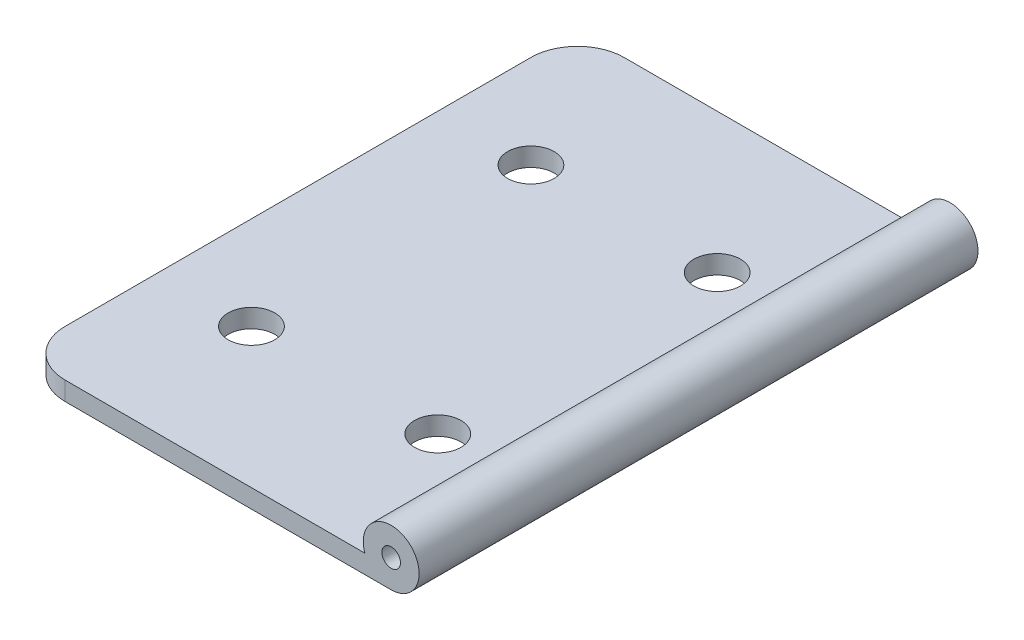
SolidWorks part; units mm, degrees
ref_plane "Front Plane" through (0, 0, 0) normal (0, 0, 1) x (1, 0, 0)
ref_plane "Top Plane" through (0, 0, 0) normal (0, 1, 0) x (1, 0, 0)
ref_plane "Right Plane" through (0, 0, 0) normal (1, 0, 0) x (0, 0, -1)
sketch "Sketch1" plane through (0, 0, 0) normal (0, 1, 0) x (1, 0, 0)
  line L0 (-32.5714, 0) -> (50.2857, 0) construction
  line L1 (0, 66.5714) -> (0, -65.7143) construction
  line L2 (-40, 30) -> (0, 30)
  line L3 (-40, 30) -> (-40, -30)
  line L4 (-40, -30) -> (0, -30)
  line L5 (0, 30) -> (0, -30)
  line L6 (-40, 30) -> (0, -30) construction
  line L7 (-40, -30) -> (0, 30) construction
  line L8 (-20, 30) -> (-20, -30) construction
  circle A0 centre (-30, 15) radius 2.5
  circle A1 centre (-10, 15) radius 2.5
  circle A2 centre (-10, -15) radius 2.5
  circle A3 centre (-30, -15) radius 2.5
  point P1 (-20, 0)
  dimension "D4" = 5
  dimension "D1" = 40
  dimension "D2" = 60
  dimension "D3" = 20
extrude "Boss-Extrude1" add sketch "Sketch1" along normal blind 2
fillet "Fillet1" radius 5 2 edges at (-40, 1, -30) (-40, 1, 30)
sketch "Sketch2" plane through (0, 0, 30) normal (0, 0, 1) x (1, 0, 0)
  line L0 (0, 3) -> (0, 2) construction
  line L1 (0, 2) -> (0, 0) construction
  circle A0 centre (0, 3) radius 3
  circle A1 centre (0, 3) radius 1
  dimension "D1" = 2
extrude "Boss-Extrude2" add sketch "Sketch2" against normal up to surface (60 mm away) up to face at (-17.5, 1, -30)
sketch "Sketch3" [suppressed] plane through (0, 0, 0) normal (0, -1, 0) x (1, 0, 0)
  line L0 (3, 0) -> (-40, 0) construction
  line L1 (3, -30) -> (3, 30) construction
  line L2 (-40, -25) -> (-40, 25) construction
  line L3 (3, 20) -> (-40, 20)
  line L4 (-35, 30) -> (0, 30) construction
  line L5 (3, -20) -> (-40, -20)
  line L7 (-3, -30) -> (3, -30)
  line L8 (-3, -30) -> (-3, 30)
  line L9 (-3, 30) -> (3, 30)
  line L10 (3, -30) -> (3, 30)
  line L11 (-3, -30) -> (3, 30) construction
  line L12 (-3, 30) -> (3, -30) construction
  point P12 (0, 0)
  dimension "D1" = 10
extrude "Cut-Extrude2" [suppressed] cut sketch "Sketch3" against normal up to next contours L8 L5 L7 L3 | L5 L10 L3 L7
sketch "Sketch4" [suppressed] plane through (0, 0, 0) normal (0, -1, 0) x (1, 0, 0)
  line L0 (3, 19.5) -> (-40, 19.5)
  line L1 (-3, -30) -> (3, -30)
  line L2 (-3, -30) -> (-3, 30)
  line L3 (-3, 30) -> (3, 30)
  line L4 (3, -30) -> (3, 30)
  line L5 (-3, -30) -> (3, 30) construction
  line L6 (-3, 30) -> (3, -30) construction
  line L7 (-40, -25) -> (-40, 25) construction
  line L8 (-35, 30) -> (0, 30) construction
  line L9 (-40, 0) -> (3, 0) construction
  line L10 (3, -19.5) -> (-40, -19.5)
  point P0 (0, 0)
  line M5 (-35, -30) -> (0, -30)
  line M6 (0, -30) -> (0, 30)
  line M7 (0, 30) -> (-35, 30)
  dimension "D1" = 10.5
extrude "Cut-Extrude3" [suppressed] cut sketch "Sketch4" against normal up to next contours L2 L0 M6 M7 | L0 L4 L3 M6 | L10 L2 M6 M5 | L4 L10 L1 M6
